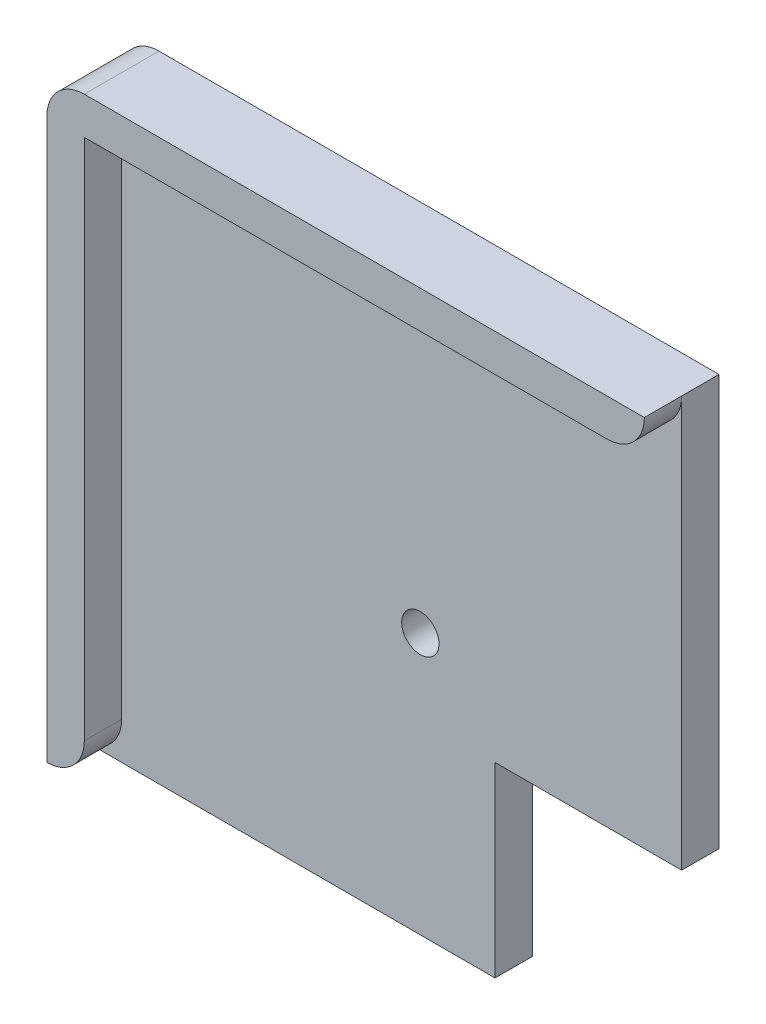
SolidWorks part; units mm, degrees
ref_plane "Front Plane" through (0, 0, 0) normal (0, 0, 1) x (1, 0, 0)
ref_plane "Top Plane" through (0, 0, 0) normal (0, 1, 0) x (1, 0, 0)
ref_plane "Right Plane" through (0, 0, 0) normal (1, 0, 0) x (0, 0, -1)
sketch "Sketch1" plane through (0, 0, 0) normal (0, 0, 1) x (1, 0, 0)
  line L0 (0, 27) -> (0, -28.875) construction
  line L1 (-22.125, 0) -> (34.125, 0) construction
  line L2 (-16, -14) -> (-16, 16)
  line L3 (-16, 16) -> (14, 16)
  line L4 (-16, -14) -> (4, -14)
  line L5 (4, -14) -> (4, -4)
  line L6 (4, -4) -> (14, -4)
  line L7 (14, -4) -> (14, 16)
  circle A0 centre (0, 0) radius 1
  dimension "D6" = 2
  dimension "D1" = 16
  dimension "D2" = 16
  dimension "D3" = 30
  dimension "D4" = 30
  dimension "D5" = 10
extrude "Boss-Extrude1" add sketch "Sketch1" along normal blind 2
sketch "Sketch3" plane through (0, 0, 2) normal (0, 0, 1) x (1, 0, 0)
  line L3 (-18, -14) -> (-16, -14)
  line L4 (-16, -14) -> (-16, 16)
  line L5 (14, 18) -> (-18, 18)
  line L6 (-18, 18) -> (-18, -14)
  line L7 (14, 18) -> (-18, 18)
  line L8 (-18, 18) -> (-18, -14)
  line L9 (-16, 16) -> (14, 16)
  line L10 (14, 16) -> (14, 18)
  dimension "D1" = 2
extrude "Boss-Extrude2" add sketch "Sketch3" along normal blind 2 and the other way blind 2
fillet "Fillet1" radius 2 3 edges at (14, 16, 3) (-16, -14, 3) (-18, 18, 2)
